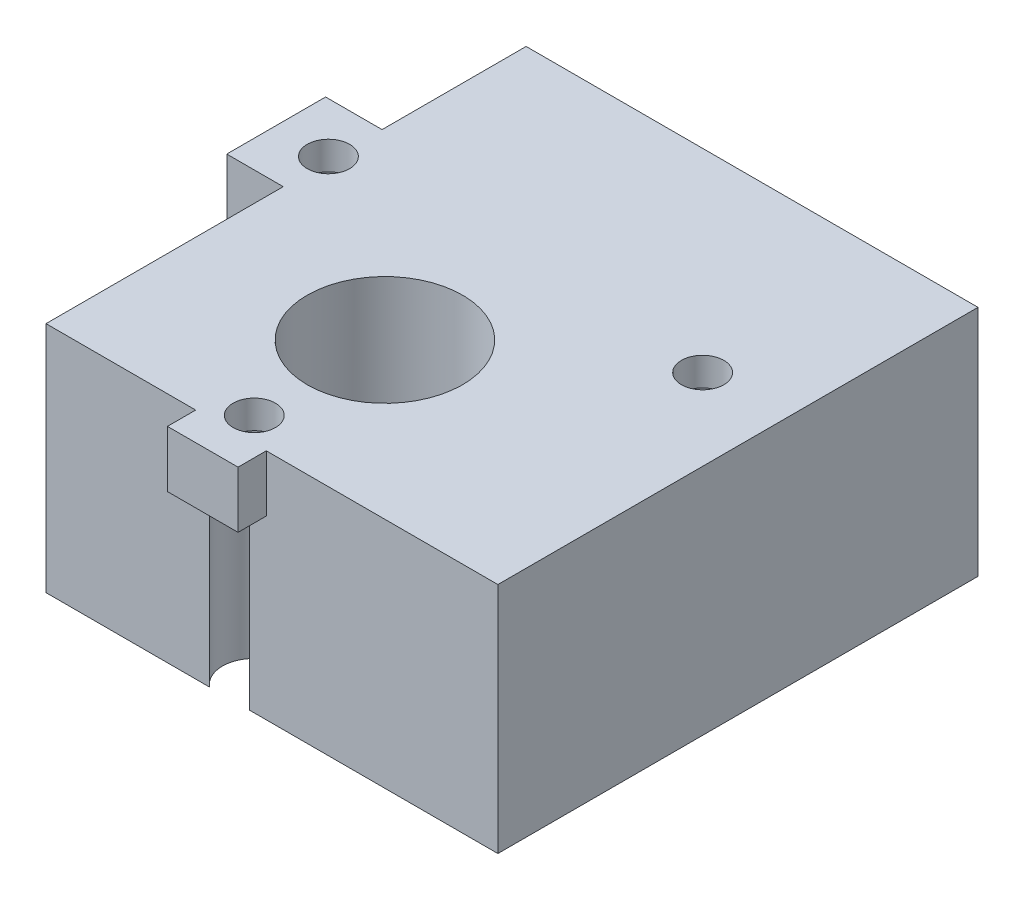
SolidWorks part; units mm, degrees
note: The reader was unsure of these and kept them because the rebuilt part matched: shared geometry of "草图1<26>", "草图1<25>", "草图2<3>", "草图2<4>", "草图1<27>".
ref_plane "前视基准面" through (0, 0, 0) normal (0, 0, 1) x (1, 0, 0)
ref_plane "上视基准面" through (0, 0, 0) normal (0, 1, 0) x (1, 0, 0)
ref_plane "右视基准面" through (0, 0, 0) normal (1, 0, 0) x (0, 0, -1)
other "Configuration Table"
sketch "草图1" plane through (0, 0, 0) normal (0, 1, 0) x (1, 0, 0)
  line L5 (-13, 23) -> (19, 23)
  line L6 (-13, 23) -> (-13, -11)
  line L7 (-13, -11) -> (19, -11)
  line L8 (19, 23) -> (19, -11)
  circle A0 centre (11.4735, 0) radius 3.3882
  circle A1 centre (-3.4891, 11.4815) radius 1.2
  circle A2 centre (8.0109, 11.4815) radius 1.2
  circle A4 centre (-3.4891, 11.4815) radius 8.5
  circle A5 centre (8.0109, 11.4815) radius 10
  circle A7 centre (4.985, 0.3868) radius 10
  circle A8 centre (4.985, 0.3868) radius 1.2
  circle A9 centre (0, 0) radius 5.5
  circle A10 centre (0, 0) radius 2.6
  dimension "D2" = 2.4
  dimension "D3" = 2.4
  dimension "D4" = 11.5
  dimension "D5" = 2.4
  dimension "D6" = 11.5
  dimension "D7" = 5.2
  dimension "D10" = 17
  dimension "D11" = 20
  dimension "D12" = 14
  dimension "D13" = 20
  dimension "D15" = 5
  dimension "D8" = 11
  dimension "D9" = 12
  dimension "D14" = 6.5
  dimension "D16" = 23
  dimension "D17" = 13
  dimension "D18" = 19
  dimension "D19" = 11
extrude "凸台-拉伸1" add sketch "草图1" along normal blind 13.5 contours L7 L8 L5 L6 | A0 | A1 | A9
extrude "凸台-拉伸3" add sketch "草图1<26>" against normal offset from surface (10.5 mm away) 3 from surface at 13.5 contours A1 up to face at (3, 0, -6) starting at face at (-3.4891, 13.5, -10.2815)
sketch "草图1<26>" plane through (0, 0, 0) normal (0, 1, 0) x (1, 0, 0) same geometry as "草图1"
extrude "凸台-拉伸2" add sketch "草图1<25>" against normal blind 3 contours L5 L8 L7 L6 | A4 | A2 | A0 | A9 | A8
sketch "草图1<25>" plane through (0, 0, 0) normal (0, 1, 0) x (1, 0, 0) same geometry as "草图1"
sketch "草图2" plane through (0, 13.5, 0) normal (0, 1, 0) x (1, 0, 0)
  line L1 (-13, 5.8) -> (-17, 5.8)
  line L2 (-13, 5.8) -> (-13, 12.8)
  line L3 (-13, 12.8) -> (-17, 12.8)
  line L4 (-17, 5.8) -> (-17, 12.8)
  line L5 (-13, -11) -> (19, -11) construction
  line L6 (2.6, -11) -> (-2.4, -11)
  line L7 (2.6, -11) -> (2.6, -13)
  line L8 (2.6, -13) -> (-2.4, -13)
  line L9 (-2.4, -11) -> (-2.4, -13)
  line L10 (-13, 23) -> (-13, -11) construction
  circle A0 centre (-13.25, 9.25) radius 1.5
  circle A1 centre (0, -9.25) radius 1.5
  circle A2 centre (13.25, 9.25) radius 1.5
  circle A3 centre (-13.25, 9.25) radius 2.25
  circle A4 centre (13.25, 9.25) radius 2.25
  circle A5 centre (0, -9.25) radius 2.25
  point P16 (2.6, -12)
  point P24 (0, 0)
  point P25 (0, -9.25)
  point P26 (0, 0)
  point P27 (13.25, 9.25)
  point P28 (-21.2675, 3.2613)
  point P29 (0, 0)
  point P30 (-13.25, 9.25)
  dimension "D7" = 3
  dimension "D8" = 4.5
  dimension "D1" = 4
  dimension "D2" = 7
  dimension "D3" = 5.8
  dimension "D4" = 2
  dimension "D5" = 5
  dimension "D6" = 2.6
extrude "凸台-拉伸4" add sketch "草图2" against normal blind 4 contours L6 L9 L8 L7 | L1 L4 L3 L2
extrude "切除-拉伸1" cut sketch "草图2<3>" against normal through all contours A2 | A0 | A1
sketch "草图2<3>" plane through (0, 13.5, 0) normal (0, 1, 0) x (1, 0, 0) same geometry as "草图2"
extrude "切除-拉伸2" cut sketch "草图2<4>" along normal offset from surface (14.5 mm away) 2 from surface at -16.5 contours A3 | A5 | A4 up to face at (13.25, 13.5, -7.75) starting at face at (13.25, -3, -7.75)
sketch "草图2<4>" plane through (0, 13.5, 0) normal (0, 1, 0) x (1, 0, 0) same geometry as "草图2"
sketch "草图3" plane through (0, -3, 0) normal (0, -1, 0) x (1, 0, 0)
  line L0 (19, -23) -> (19, 11) construction
  line L1 (-13, -23) -> (19, -23) construction
  line L2 (1.4142, 11) -> (19, 11) construction
  line L3 (-13, 11) -> (-1.4142, 11) construction
  line L4 (-13, -7.0139) -> (-13, 11) construction
  circle A0 centre (-10, 8) radius 0.75
  circle A1 centre (17, -21) radius 0.75
  circle A2 centre (16, 8) radius 0.75
  point P16 (-4.8313, 6.5167)
  dimension "D1" = 1.5
  dimension "D2" = 2
  dimension "D3" = 2
  dimension "D4" = 3
  dimension "D5" = 3
  dimension "D6" = 3
  dimension "D7" = 3
extrude "切除-拉伸3" cut sketch "草图3" against normal blind 4
extrude "凸台-拉伸5" add sketch "草图1<27>" along normal through all from surface at -3 contours A0 starting at face at (-10, -3, 7.25)
sketch "草图1<27>" plane through (0, 0, 0) normal (0, 1, 0) x (1, 0, 0) same geometry as "草图1"
